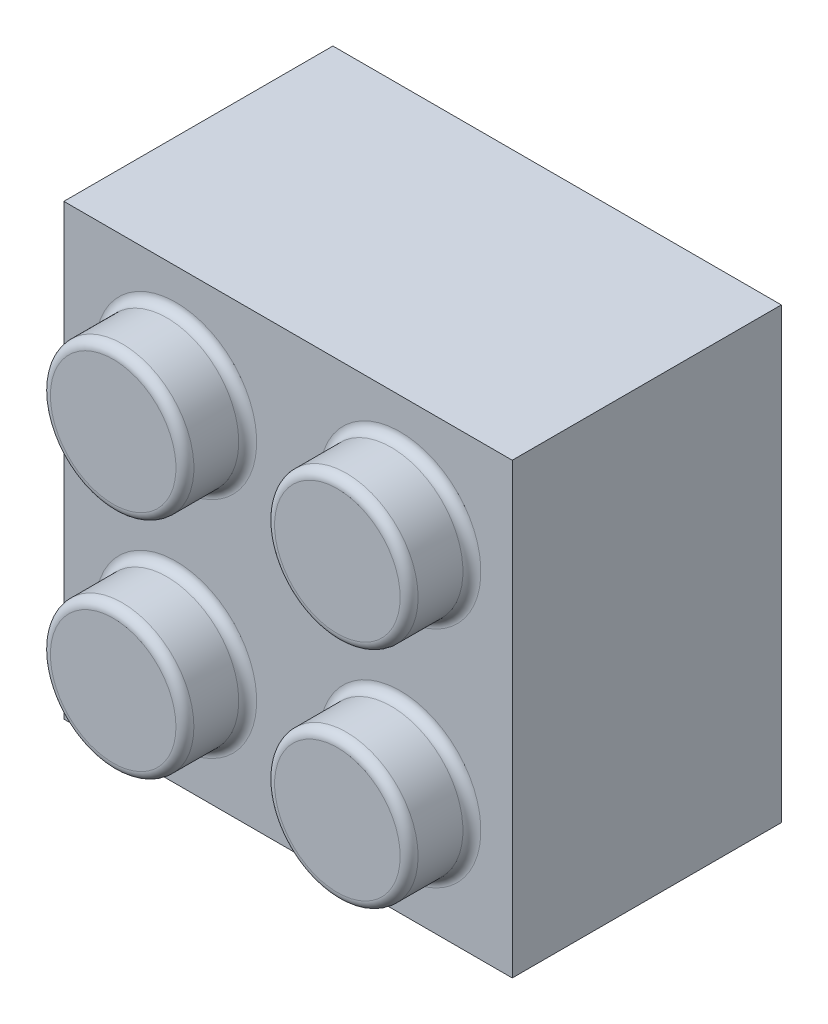
SolidWorks part; units mm, degrees
ref_plane "Plan de face" through (0, 0, 0) normal (0, 0, 1) x (1, 0, 0)
ref_plane "Plan de dessus" through (0, 0, 0) normal (0, 1, 0) x (1, 0, 0)
ref_plane "Plan de droite" through (0, 0, 0) normal (1, 0, 0) x (0, 0, -1)
sketch "Esquisse2" plane through (0, 0, 0) normal (0, 0, 1) x (1, 0, 0)
  line L0 (-78.6329, 0) -> (78.6329, 0) construction
  line L1 (0, 53.996) -> (0, -53.996) construction
  line L2 (-50, 50) -> (50, 50)
  line L3 (50, 50) -> (50, -50)
  line L4 (50, -50) -> (-50, -50)
  line L5 (-50, -50) -> (-50, 50)
  point P7 (0, 0)
  point P10 (0, 0)
  dimension "D1" = 100
extrude "Boss.-Extru.1" add sketch "Esquisse2" along normal blind 60
sketch "Esquisse3" plane through (0, 0, 60) normal (0, 0, 1) x (1, 0, 0)
  line L0 (0, 50) -> (0, -50)
  line L1 (50, 50) -> (-50, 50) construction
  line L2 (-50, -50) -> (50, -50) construction
  line L3 (50, 0) -> (-50, 0)
  line L4 (50, -50) -> (50, 50) construction
  line L5 (-50, 50) -> (-50, -50) construction
  line L6 (50, 50) -> (0, 0)
  circle A0 centre (25, 25) radius 16
  circle A1 centre (25, -25) radius 16
  circle A2 centre (-25, -25) radius 16
  circle A3 centre (-25, 25) radius 16
  dimension "D1" = 32
extrude "Boss.-Extru.2" add sketch "Esquisse3" along normal blind 14 contours L6 A0 | L6 A0 | A1 | A2 | A3 region at (29.8017, 20.1983, 60) region at (20.1983, 29.8017, 60) region at (25, -25, 60) region at (-25, -25, 60)
sketch "Esquisse4" plane through (0, 0, 0) normal (0, 0, -1) x (-1, 0, 0)
  line L0 (0, 50) -> (0, -50) construction
  line L1 (-50, 50) -> (50, 50) construction
  line L2 (50, -50) -> (-50, -50) construction
  line L3 (50, 0) -> (-50, 0) construction
  line L4 (-50, -50) -> (-50, 50) construction
  line L5 (50, 50) -> (50, -50) construction
  line L6 (-42, 42) -> (-42, -42)
  line L7 (-42, -42) -> (42, -42)
  line L8 (42, -42) -> (42, 42)
  line L9 (42, 42) -> (-42, 42)
  circle A0 centre (0, 0) radius 18.5
  circle A1 centre (0, 0) radius 12
  dimension "D2" = 37
  dimension "D3" = 24
  dimension "D1" = 8
extrude "Enlèv. mat.-Extru.1" cut sketch "Esquisse4" against normal blind 50 contours L8 L9 L6 L7 A0 | A1 region at (0, 40.8121, 0) region at (0, 0, 0)
fillet "Congé9" radius 2 10 edges at (-18.5, 0, 50) (-18.5, 0, 0) (41, -25, 60) (41, -25, 74) (-41, -25, 60) (-9, -25, 74) (9, 25, 60) (41, 25, 74) (-41, 25, 60) (-41, 25, 74)
